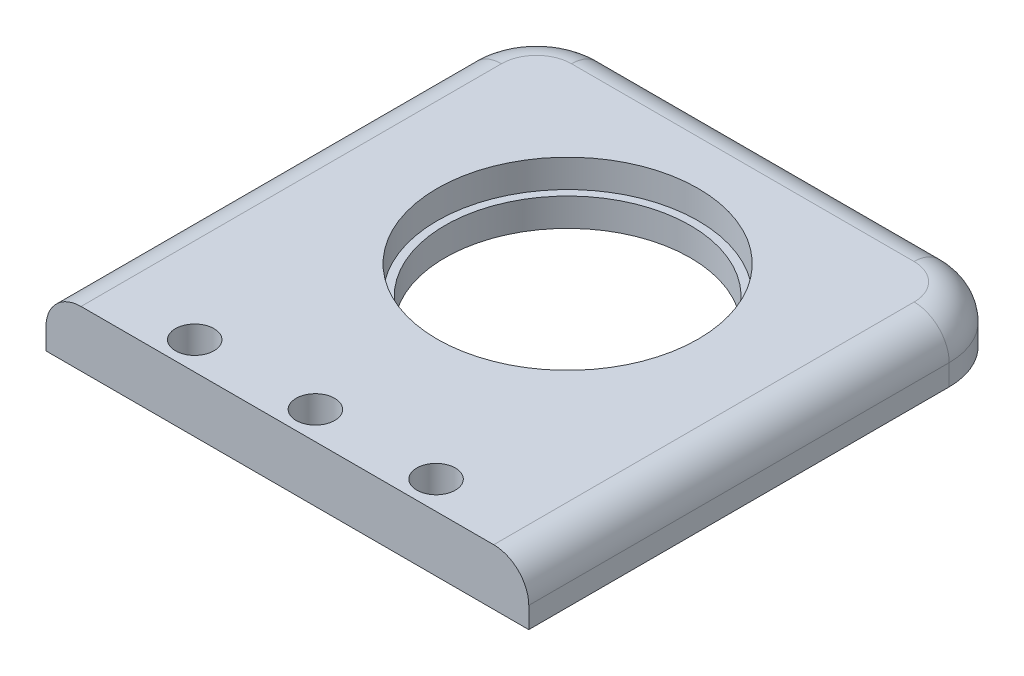
SolidWorks part; units mm, degrees
ref_plane "Front Plane" through (0, 0, 0) normal (0, 0, 1) x (1, 0, 0)
ref_plane "Top Plane" through (0, 0, 0) normal (0, 1, 0) x (1, 0, 0)
ref_plane "Right Plane" through (0, 0, 0) normal (1, 0, 0) x (0, 0, -1)
sketch "Sketch1" plane through (0, 0, 0) normal (0, 1, 0) x (1, 0, 0)
  line L0 (-33.7277, -40) -> (35.1723, -40)
  line L1 (-33.7277, -40) -> (-33.7277, 30)
  line L2 (-33.7277, 30) -> (35.1723, 30)
  line L3 (35.1723, -40) -> (35.1723, 30)
  circle A0 centre (0.7223, 0) radius 18.63
  circle A1 centre (0.7223, -36) radius 2.75
  circle A2 centre (-16.5027, -36) radius 2.75
  circle A3 centre (17.9473, -36) radius 2.75
  dimension "D1" = 30
  dimension "D2" = 68.9
  dimension "D3" = 34.45
  dimension "D4" = 34.45
  dimension "D5" = 17.225
  dimension "D6" = 17.225
  dimension "D7" = 4
  dimension "D8" = 70
  dimension "D9" = 4
extrude "Boss-Extrude1" add sketch "Sketch1" along normal blind 8
fillet "Fillet1" radius 10 2 edges at (35.1723, 4, -30) (-33.7277, 4, -30)
fillet "Fillet2" radius 5 5 edges at (32.2434, 8, -27.0711) (0.7223, 8, -30) (-30.7987, 8, -27.0711) (35.1723, 8, 10) (-33.7277, 8, 10)
sketch "Sketch2" plane through (0, 0, 0) normal (0, -1, 0) x (1, 0, 0)
  circle A0 centre (0.7223, 0) radius 17.5
  circle A1 centre (0.7223, 0) radius 18.63
extrude "Boss-Extrude2" add sketch "Sketch2" against normal blind 4
